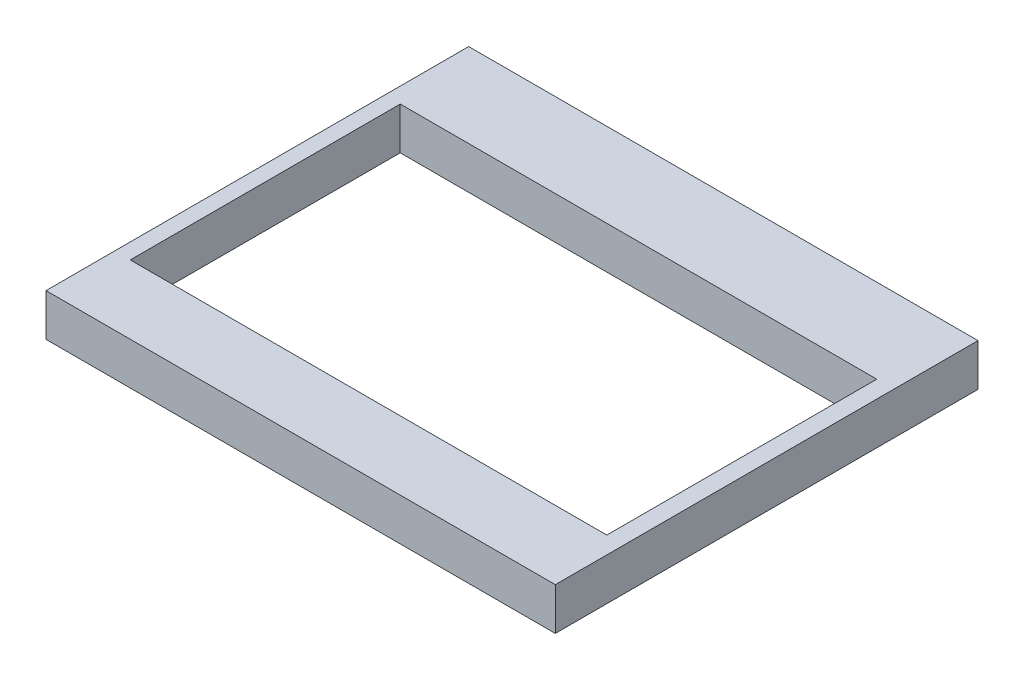
SolidWorks part; units mm, degrees
material "Polyurethane Foam Rigid"
ref_plane "X-Y Datum" through (0, 0, 0) normal (0, 0, 1) x (1, 0, 0)
ref_plane "X-Z Datum" through (0, 0, 0) normal (0, 1, 0) x (1, 0, 0)
ref_plane "Y-Z Datum" through (0, 0, 0) normal (1, 0, 0) x (0, 0, -1)
sketch "Sketch1" plane through (0, 0, 0) normal (0, 0, 1) x (1, 0, 0)
  line L1 (-153.0248, -12.7) -> (153.0248, -12.7)
  line L2 (-153.0248, -12.7) -> (-153.0248, 12.7)
  line L3 (-153.0248, 12.7) -> (153.0248, 12.7)
  line L4 (153.0248, -12.7) -> (153.0248, 12.7)
  line L5 (-153.0248, -12.7) -> (153.0248, 12.7) construction
  line L6 (-153.0248, 12.7) -> (153.0248, -12.7) construction
  point P0 (0, 0)
  dimension "D1" = 25.4
  dimension "D2" = 306.0497
extrude "Boss-Extrude1" add sketch "Sketch1" against normal blind 254
sketch "Sketch2" plane through (0, -12.7, 0) normal (0, -1, 0) x (1, 0, 0)
  line L0 (0, 0) -> (0, -254) construction
  line L1 (-178.4248, -254) -> (178.4248, -254) construction
  line L2 (-149.8502, -41.275) -> (149.8498, -41.275) construction
  line L3 (-143.6774, -203.5082) -> (142.6839, -203.5082)
  line L4 (-143.6774, -203.5082) -> (-143.6774, -41.275)
  line L5 (-143.6774, -41.275) -> (142.6839, -41.275)
  line L6 (142.6839, -203.5082) -> (142.6839, -41.275)
  line L7 (-143.6774, -203.5082) -> (142.6839, -41.275) construction
  line L8 (-143.6774, -41.275) -> (142.6839, -203.5082) construction
  line L15 (178.4248, -254) -> (178.4248, 0) construction
  point P5 (-0.4968, -122.3916)
  dimension "D1" = 35.741
extrude "Cut-Extrude1" cut sketch "Sketch2" against normal through all
